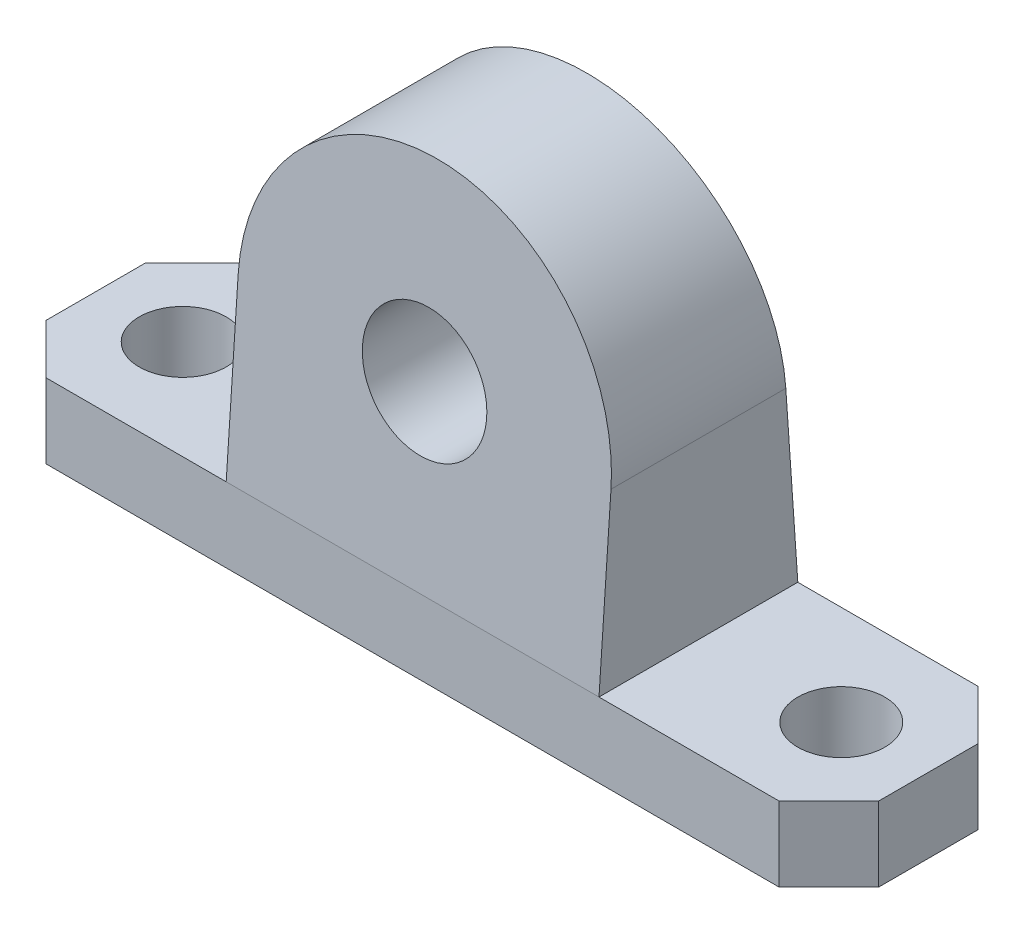
SolidWorks part; units mm, degrees
ref_plane "Front Plane" through (0, 0, 0) normal (0, 0, 1) x (1, 0, 0)
ref_plane "Top Plane" through (0, 0, 0) normal (0, 1, 0) x (1, 0, 0)
ref_plane "Right Plane" through (0, 0, 0) normal (1, 0, 0) x (0, 0, -1)
sketch "Sketch2" plane through (0, 0, 0) normal (0, 1, 0) x (1, 0, 0)
  line L0 (-29.5, 8) -> (-33.5, 4)
  line L1 (-29.5, -8) -> (29.5, -8)
  line L2 (-33.5, -4) -> (-33.5, 4)
  line L3 (-29.5, 8) -> (29.5, 8)
  line L4 (33.5, -4) -> (33.5, 4)
  line L5 (-33.5, -8) -> (33.5, 8) construction
  line L6 (-33.5, 8) -> (33.5, -8) construction
  line L7 (29.5, 8) -> (33.5, 4)
  line L8 (33.5, -4) -> (29.5, -8)
  line L9 (-33.5, -4) -> (-29.5, -8)
  point P0 (0, 0)
  dimension "D1" = 16
  dimension "D2" = 67
  dimension "D3" = 4
  dimension "D4" = 4
  dimension "D5" = 4
  dimension "D6" = 4
  dimension "D7" = 4
  dimension "D8" = 4
  dimension "D9" = 4
  dimension "D10" = 4
extrude "Boss-Extrude2" add sketch "Sketch2" along normal blind 6
sketch "Sketch3" plane through (0, 6, 0) normal (0, 1, 0) x (1, 0, 0)
  line L0 (29.5, 8) -> (-29.5, 8) construction
  line L1 (-15, -8) -> (15, -8)
  line L2 (-15, -8) -> (-15, 8)
  line L3 (-15, 8) -> (15, 8)
  line L4 (15, -8) -> (15, 8)
  line L5 (-15, -8) -> (15, 8) construction
  line L6 (-15, 8) -> (15, -8) construction
  point P0 (0, 0)
  dimension "D1" = 30
extrude "Boss-Extrude3" add sketch "Sketch3" along normal blind 29
sketch "Sketch4" plane through (0, 0, 8) normal (0, 0, 1) x (1, 0, 0)
  line L0 (-15, 35) -> (15, 35) construction
  line L1 (15, 35) -> (15, 6) construction
  line L2 (-15, 35) -> (-15, 6) construction
  line L3 (15, 35) -> (15, 20)
  line L4 (-15, 35) -> (15, 35)
  line L5 (-15, 35) -> (-15, 20)
  arc A0 (15, 20) -> (-15, 20) centre (0, 20) ccw
  line M4 (15, 6) -> (15, 35)
  line M5 (15, 35) -> (-15, 35)
  line M6 (-15, 35) -> (-15, 6)
  dimension "D1" = 30
extrude "Cut-Extrude1" cut sketch "Sketch4" against normal up to surface (16 mm away) contours A0 L4 M6 | A0 M4 M5 region at (-11.6495, 31.6495, 8) region at (11.6495, 31.6495, 8) up to face at (0, 11.75, -8)
sketch "Sketch5" plane through (-15, 0, 0) normal (-1, 0, 0) x (0, 0, 1)
  line L1 (8, 35) -> (-8, 35) construction
  line L2 (8, 20) -> (8, 35) construction
  line L3 (-6, 35) -> (-8, 6)
  line L4 (-6, 35) -> (-8, 35)
  line L5 (8, 6) -> (6, 35)
  line L6 (-8, 35) -> (-8, 20) construction
  line L7 (-8, 35) -> (-8, 6)
  line L8 (6, 35) -> (8, 35)
  line L9 (8, 35) -> (8, 6)
  dimension "D1" = 12
  dimension "D2" = 2
extrude "Cut-Extrude2" cut sketch "Sketch5" against normal blind 30
sketch "Sketch6" plane through (0, 0, 0) normal (0, -1, 0) x (1, 0, 0)
  line L0 (33.5, 4) -> (33.5, -4) construction
  circle A0 centre (-26.5, 0) radius 3.5
  circle A1 centre (26.5, 0) radius 3.5
  dimension "D1" = 7
  dimension "D2" = 7
  dimension "D3" = 53
  dimension "D4" = 7
extrude "Cut-Extrude3" cut sketch "Sketch6" against normal blind 6
sketch "Sketch7" plane through (0, 0, -8) normal (0, 0, -1) x (-1, 0, 0)
  circle A0 centre (0, 20) radius 5
  dimension "D1" = 10
extrude "Cut-Extrude4" cut sketch "Sketch7" against normal up to surface (15.0345 mm away) up to face at (0, 16.75, 7.2586)
sketch "Sketch8" plane through (0, 0, -8) normal (0, 0, -1) x (-1, 0, 0)
  circle A0 centre (0, 20) radius 7
  circle A1 centre (0, 20) radius 5 construction
  circle A2 centre (0, 20) radius 5
  dimension "D1" = 14
extrude "Boss-Extrude4" add sketch "Sketch8" against normal up to surface and the other way blind 1 up to face at (0, 15, -7.3793)
